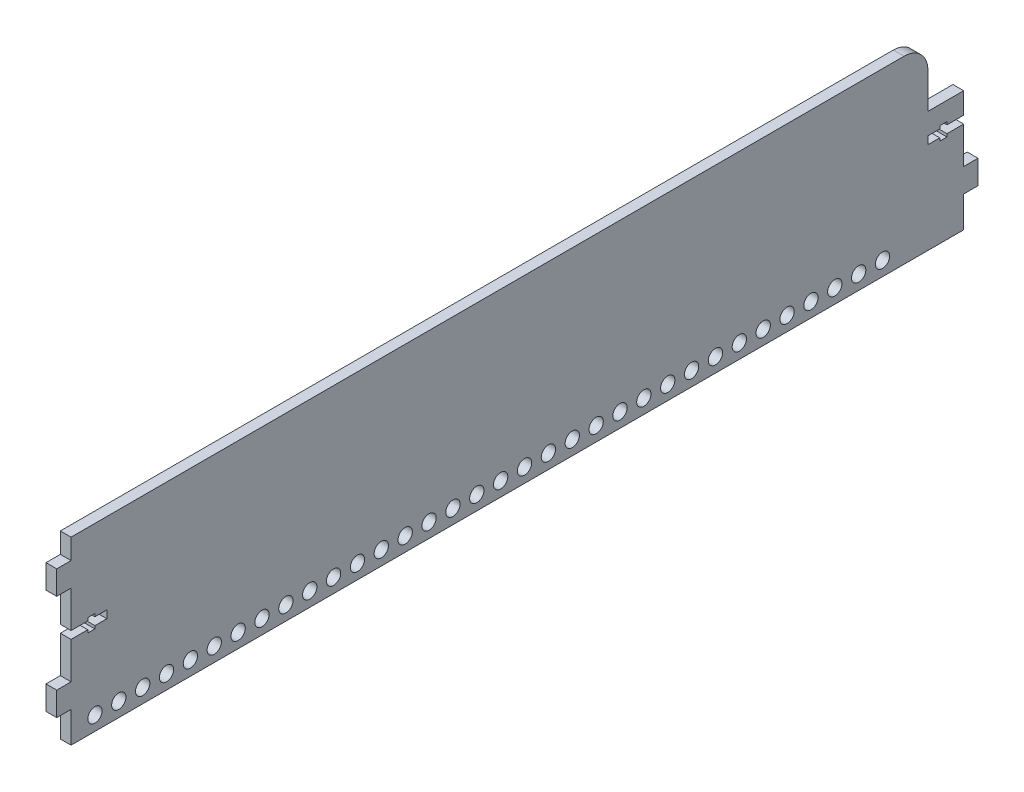
SolidWorks part; units mm, degrees
ref_plane "Front Plane" through (0, 0, 0) normal (0, 0, 1) x (1, 0, 0)
ref_plane "Top Plane" through (0, 0, 0) normal (0, 1, 0) x (1, 0, 0)
ref_plane "Right Plane" through (0, 0, 0) normal (1, 0, 0) x (0, 0, -1)
sketch "Sketch1" plane through (0, 0, 0) normal (1, 0, 0) x (0, 0, -1)
  line L1 (-187, -40) -> (187, -40)
  line L2 (-187, -40) -> (-187, 40)
  line L3 (-187, 40) -> (187, 40)
  line L4 (187, -40) -> (187, 40)
  line L5 (-187, -40) -> (187, 40) construction
  line L6 (-187, 40) -> (187, -40) construction
  point P0 (0, 0)
  dimension "D1" = 80
  dimension "D2" = 374
extrude "Boss-Extrude1" add sketch "Sketch1" along normal blind 4.5
sketch "Sketch4" plane through (0, 0, 187) normal (0, 0, 1) x (1, 0, 0)
  line L1 (4.5, 27) -> (0, 27) construction
  line L2 (4.5, 17) -> (4.5, 27) construction
  line L3 (0, 27) -> (0, 17) construction
  line L4 (0, 17) -> (4.5, 17) construction
  line L7 (4.5, -17) -> (0, -17) construction
  line L8 (4.5, -27) -> (4.5, -17) construction
  line L9 (0, -17) -> (0, -27) construction
  line L10 (0, -27) -> (4.5, -27) construction
  line L13 (4.5, 27) -> (0, 27)
  line L14 (4.5, 17) -> (4.5, 27)
  line L15 (0, 27) -> (0, 17)
  line L16 (0, 17) -> (4.5, 17)
  line L17 (4.5, -17) -> (0, -17)
  line L18 (4.5, -27) -> (4.5, -17)
  line L19 (0, -17) -> (0, -27)
  line L20 (0, -27) -> (4.5, -27)
extrude "Boss-Extrude2" add sketch "Sketch4" along normal blind 6
sketch "Sketch5" plane through (0, 0, 0) normal (-1, 0, 0) x (0, 0, 1)
  line L0 (187, 17) -> (187, -17) construction
  line L7 (0, 0) -> (0, -20.5925) construction
  line L8 (-187, 1.6) -> (-180, 1.6)
  line L9 (-177, 2.8) -> (-180, 2.8)
  line L10 (-177, 1.6) -> (-172, 1.6)
  line L11 (-172, -1.6) -> (-172, 1.6)
  line L12 (-177, -1.6) -> (-172, -1.6)
  line L13 (-177, -2.8) -> (-180, -2.8)
  line L14 (-187, -1.6) -> (-180, -1.6)
  line L15 (-180, -2.8) -> (-180, -1.6)
  line L16 (-180, 1.6) -> (-180, 2.8)
  line L17 (-177, 1.6) -> (-177, 2.8)
  line L18 (-177, -2.8) -> (-177, -1.6)
  line L19 (193, -1.6) -> (193, 1.6) construction
  line L20 (193, -1.6) -> (193, 1.6)
  line L21 (193, 0) -> (146.4296, 0) construction
  line L25 (187, -1.6) -> (187, 1.6)
  line L26 (177, -2.8) -> (177, -1.6)
  line L27 (177, 1.6) -> (177, 2.8)
  line L28 (180, 1.6) -> (180, 2.8)
  line L29 (180, -2.8) -> (180, -1.6)
  line L30 (187, -1.6) -> (180, -1.6)
  line L31 (177, -2.8) -> (180, -2.8)
  line L32 (177, -1.6) -> (172, -1.6)
  line L33 (172, -1.6) -> (172, 1.6)
  line L34 (177, 1.6) -> (172, 1.6)
  line L35 (177, 2.8) -> (180, 2.8)
  line L36 (187, 1.6) -> (180, 1.6)
  line L37 (-187, -1.6) -> (-187, 1.6)
  line L38 (-193, -1.6) -> (-193, 1.6)
  point P0 (187, 0)
  dimension "D1" = 15
  dimension "D2" = 5.6
  dimension "D3" = 3.2
  dimension "D4" = 7
  dimension "D5" = 3
extrude "Cut-Extrude3" cut sketch "Sketch5" against normal up to next contours L25 L36 L28 L35 L27 L34 L33 L32 L26 L31 L29 L30 | L37 L14 L15 L13 L18 L12 L11 L10 L17 L9 L16 L8 region at (0, 0, -179.3696) region at (0, 0, 179.3696)
sketch "Sketch7" plane through (0, 0, -187) normal (0, 0, -1) x (-1, 0, 0)
  line L6 (-4.5, -17) -> (0, -17)
  line L7 (-4.5, -17) -> (-4.5, -27)
  line L8 (-4.5, -27) -> (0, -27)
  line L9 (0, -17) -> (0, -27)
  line L15 (-4.5, -40) -> (-4.5, -1.6) construction
  line L16 (0, -40) -> (0, -1.6) construction
  line L17 (-4.5, -17) -> (0, -17) construction
  line L18 (0, -27) -> (-4.5, -27) construction
extrude "Boss-Extrude3" add sketch "Sketch7" along normal blind 6
sketch "Sketch8" plane through (0, 40, 0) normal (0, 1, 0) x (1, 0, 0)
  line L1 (0, 187) -> (4.5, 187)
  line L2 (0, 187) -> (0, -187)
  line L3 (0, -187) -> (4.5, -187)
  line L4 (4.5, 187) -> (4.5, -187)
extrude "Cut-Extrude4" cut sketch "Sketch8" against normal blind 4.5
sketch "Sketch9" plane through (0, 35.5, 0) normal (0, 1, 0) x (1, 0, 0)
  line L0 (0, 187) -> (0, -187) construction
  line L1 (0, 187) -> (4.5, 187)
  line L2 (0, 187) -> (0, 172)
  line L3 (0, 172) -> (4.5, 172)
  line L4 (4.5, 187) -> (4.5, 172)
  line L5 (4.5, -187) -> (4.5, 187) construction
  dimension "D2" = 15
extrude "Cut-Extrude5" cut sketch "Sketch9" against normal blind 25
fillet "Fillet1" radius 10 1 edges at (2.25, 35.5, -172)
sketch "Sketch10" plane through (0, 0, 0) normal (-1, 0, 0) x (0, 0, 1)
  line L0 (187, -40) -> (-187, -40) construction
  line L1 (187, -27) -> (187, -40) construction
  circle A0 centre (177, -34) radius 3
  circle A1 centre (167, -34) radius 3
  circle A2 centre (157, -34) radius 3
  circle A3 centre (147, -34) radius 3
  circle A4 centre (137, -34) radius 3
  circle A5 centre (127, -34) radius 3
  circle A6 centre (117, -34) radius 3
  circle A7 centre (107, -34) radius 3
  circle A8 centre (97, -34) radius 3
  circle A9 centre (87, -34) radius 3
  circle A10 centre (77, -34) radius 3
  circle A11 centre (67, -34) radius 3
  circle A12 centre (57, -34) radius 3
  circle A13 centre (47, -34) radius 3
  circle A14 centre (37, -34) radius 3
  circle A15 centre (27, -34) radius 3
  circle A16 centre (17, -34) radius 3
  circle A17 centre (7, -34) radius 3
  circle A18 centre (-3, -34) radius 3
  circle A19 centre (-13, -34) radius 3
  circle A20 centre (-23, -34) radius 3
  circle A21 centre (-33, -34) radius 3
  circle A22 centre (-43, -34) radius 3
  circle A23 centre (-53, -34) radius 3
  circle A24 centre (-63, -34) radius 3
  circle A25 centre (-73, -34) radius 3
  circle A26 centre (-83, -34) radius 3
  circle A27 centre (-93, -34) radius 3
  circle A28 centre (-103, -34) radius 3
  circle A29 centre (-113, -34) radius 3
  circle A30 centre (-123, -34) radius 3
  circle A31 centre (-133, -34) radius 3
  circle A32 centre (-143, -34) radius 3
  circle A33 centre (-153, -34) radius 3
  dimension "D1" = 6
  dimension "D2" = 6
  dimension "D3" = 10
  dimension "D4" = 34
extrude "Cut-Extrude6" cut sketch "Sketch10" against normal up to next (4.5 mm away)
